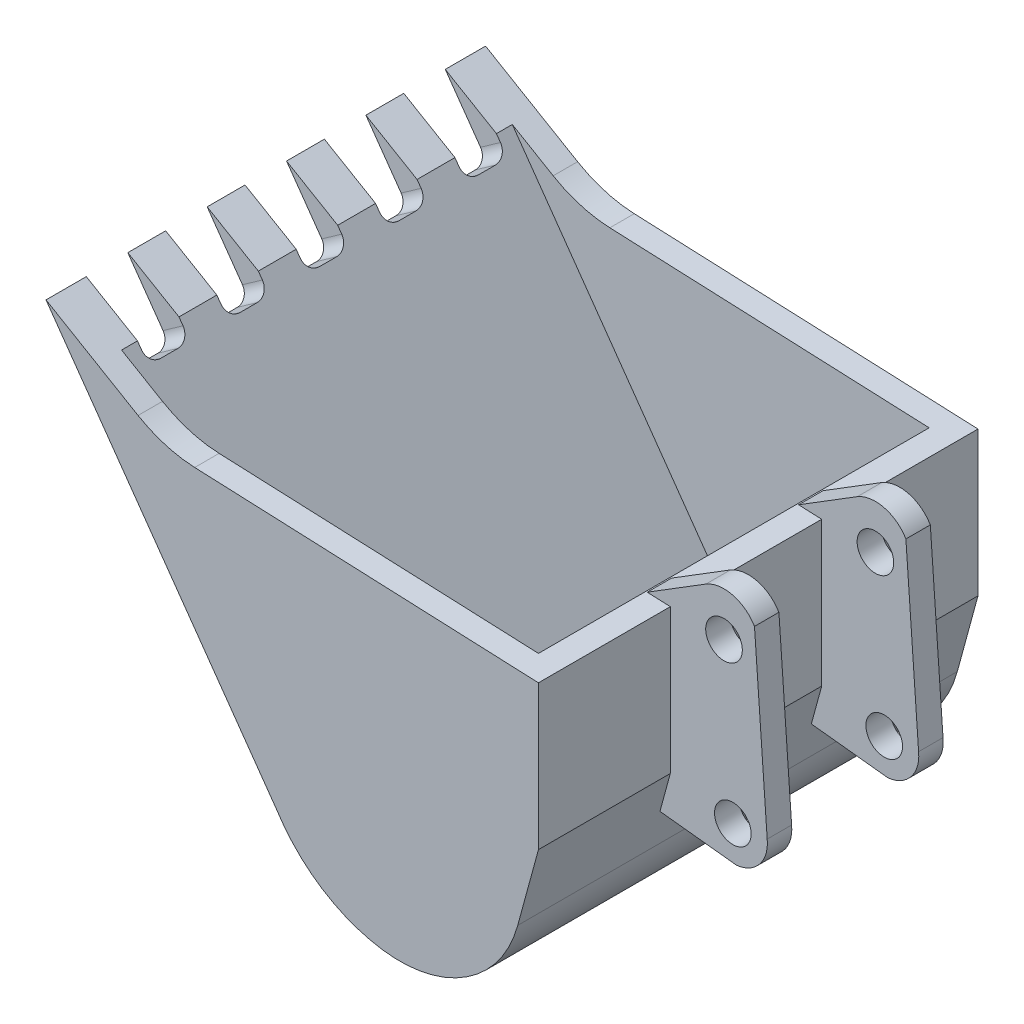
SolidWorks part; units mm, degrees
ref_plane "前视基准面" through (0, 0, 0) normal (0, 0, 1) x (1, 0, 0)
ref_plane "上视基准面" through (0, 0, 0) normal (0, 1, 0) x (1, 0, 0)
ref_plane "右视基准面" through (0, 0, 0) normal (1, 0, 0) x (0, 0, -1)
sketch "草图1" plane through (0, 0, 0) normal (0, 0, 1) x (1, 0, 0)
  line L0 (304, 402) -> (1520, 402) construction
  line L1 (85.0642, 101.1323) -> (168.9792, 46.7423) construction
  line L2 (151.7889, 43.508) -> (159.3279, 39.0793)
  line L3 (163.9682, 37.7106) -> (192.1194, 36.5136)
  line L4 (192.1194, 36.5136) -> (192.1194, 24.6808)
  line L5 (192.1194, 24.6808) -> (190.4235, 18.4598)
  line L6 (151.7889, 43.508) -> (170.6801, 16.7977)
  arc A0 (170.6801, 16.7977) -> (179.3324, 11.1947) centre (181.1172, 23.4328) ccw
  arc A3 (159.3279, 39.0793) -> (163.9682, 37.7106) centre (164.393, 47.7016) ccw
  arc A4 (190.4235, 18.4598) -> (179.3324, 11.1947) centre (180.7756, 21.09) cw
  dimension "D3" = 10
  dimension "D1" = 100
extrude "凸台-拉伸1" add sketch "草图1" along normal blind 18 and the other way blind 18 contours L3 L4 L5 A4 A0 L6 L2 A3
shell "抽壳1" thickness 2 removed face at (155.5584, 41.2936, 0) removed face at (161.606, 38.2525, 0) removed face at (178.0438, 37.1121, 0)
sketch "草图3" plane through (0, 0, 0) normal (0, 0, 1) x (1, 0, 0)
  line L0 (190.2264, 36.5941) -> (195.0358, 39.5755)
  line L1 (163.9682, 37.7106) -> (192.1194, 36.5136) construction
  line L2 (199.0137, 38.5615) -> (200.0542, 23.9944)
  line L3 (191.2714, 21.5703) -> (197.5368, 20.8861)
  line L4 (192.1194, 24.6808) -> (190.4235, 18.4598) construction
  line L12 (159.3279, 39.0793) -> (151.7889, 43.508)
  line L13 (151.7889, 43.508) -> (170.6801, 16.7977)
  line L16 (190.4235, 18.4598) -> (192.1194, 24.6808)
  line L17 (192.1194, 24.6808) -> (192.1194, 36.5136)
  line L18 (192.1194, 36.5136) -> (163.9682, 37.7106)
  line L19 (159.3279, 39.0793) -> (151.7889, 43.508)
  line L20 (151.7889, 43.508) -> (170.6801, 16.7977)
  line L23 (190.4235, 18.4598) -> (192.1194, 24.6808)
  line L24 (192.1194, 24.6808) -> (192.1194, 36.5136)
  line L25 (192.1194, 36.5136) -> (163.9682, 37.7106)
  arc A0 (195.0358, 39.5755) -> (199.0137, 38.5615) centre (196.5178, 37.0796) cw
  arc A1 (197.5368, 20.8861) -> (200.0542, 23.9944) centre (197.2414, 23.699) ccw
  circle A2 centre (196.5178, 36.3761) radius 1.5
  circle A3 centre (197.2414, 23.699) radius 1.5
  arc A9 (159.3279, 39.0793) -> (163.9682, 37.7106) centre (164.393, 47.7016) ccw
  arc A12 (170.6801, 16.7977) -> (179.3324, 11.1947) centre (181.1172, 23.4328) ccw
  arc A13 (179.3324, 11.1947) -> (190.4235, 18.4598) centre (180.7756, 21.09) ccw
  arc A14 (159.3279, 39.0793) -> (163.9682, 37.7106) centre (164.393, 47.7016) ccw
  arc A17 (170.6801, 16.7977) -> (179.3324, 11.1947) centre (181.1172, 23.4328) ccw
  arc A18 (179.3324, 11.1947) -> (190.4235, 18.4598) centre (180.7756, 21.09) ccw
  dimension "D1" = 3
  dimension "D2" = 3
  dimension "D3" = 0
extrude "凸台-拉伸4" add sketch "草图3" along normal blind 2 from offset 5.2 contours L3 A1 L2 A0 L0 L25 L24 L23 A3 A2 region at (195.6921, 30.022, 0)
mirror "镜向1" about plane through (0, 0, 0) normal (0, 0, 1) of "凸台-拉伸4"
sketch "草图4" plane through (121.6889, 86.0663, 0) normal (-0.8164, -0.5774, 0) x (0, 0, 1)
  line L0 (0, -52.1269) -> (0, -84.8426) construction
  line L1 (-18, -52.1269) -> (18, -52.1269) construction
  line L2 (-18, -84.8426) -> (18, -84.8426) construction
  line L4 (-1.7, -52.1269) -> (1.7, -52.1269)
  line L5 (-1.7, -52.1269) -> (-1.7, -58.1269)
  line L6 (-1.7, -58.1269) -> (1.7, -58.1269)
  line L7 (1.7, -52.1269) -> (1.7, -58.1269)
  dimension "D1" = 3.4
  dimension "D2" = 6
  dimension "D3" = 1.7
extrude "切除-拉伸1" cut sketch "草图4" against normal blind 10
pattern_linear "阵列(线性)1" count 3 spacing 6.5 along (0, 0, -1) count 3 spacing 6.5 along (0, 0, 1) of "切除-拉伸1" pattern seed only yes
fillet "圆角1" radius 1 10 edges at (156.07, 39.1868, -8.2) (156.07, 39.1868, -4.8) (156.07, 39.1868, 11.3) (156.07, 39.1868, 14.7) (156.07, 39.1868, 4.8) (156.07, 39.1868, 8.2) (156.07, 39.1868, -11.3) (156.07, 39.1868, -14.7) (156.07, 39.1868, 1.7) (156.07, 39.1868, -1.7)
